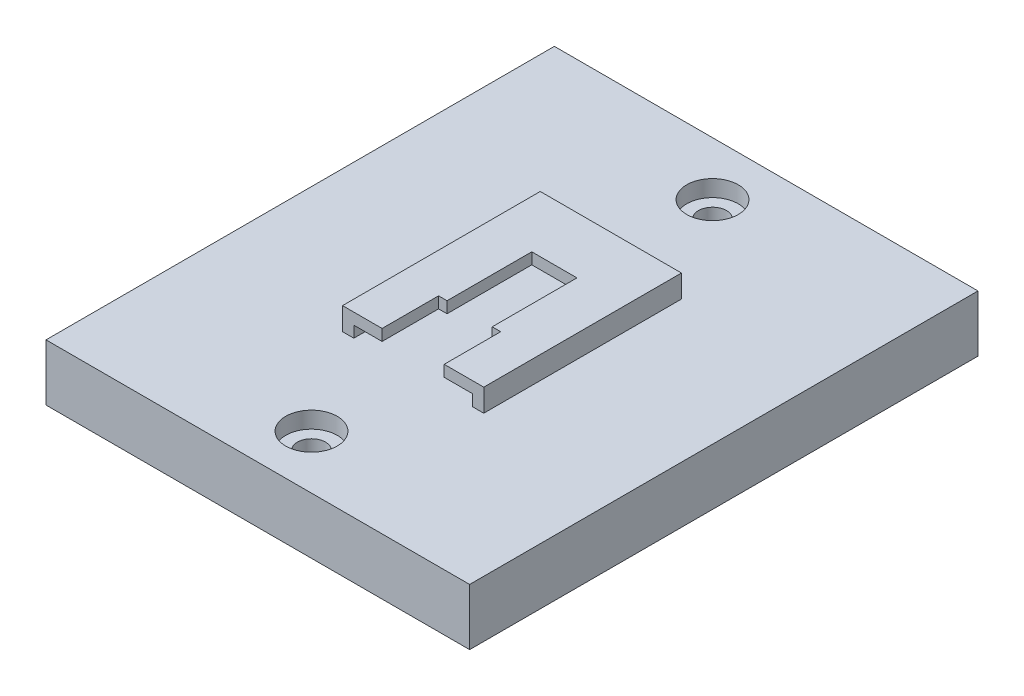
SolidWorks part; units mm, degrees
ref_plane "Front Plane" through (0, 0, 0) normal (0, 0, 1) x (1, 0, 0)
ref_plane "Top Plane" through (0, 0, 0) normal (0, 1, 0) x (1, 0, 0)
ref_plane "Right Plane" through (0, 0, 0) normal (1, 0, 0) x (0, 0, -1)
sketch "Sketch1" plane through (0, 0, 0) normal (0, 1, 0) x (1, 0, 0)
  line L0 (0, 23.0591) -> (0, -29.2863) construction
  line L1 (-12.5, 17.5) -> (12.5, 17.5)
  line L2 (-12.5, 17.5) -> (-12.5, -17.5)
  line L3 (-12.5, -17.5) -> (12.5, -17.5)
  line L4 (12.5, 17.5) -> (12.5, -17.5)
  line L5 (-12.5, 17.5) -> (12.5, -17.5) construction
  line L6 (-12.5, -17.5) -> (12.5, 17.5) construction
  line L7 (-5.5, -17.5) -> (5.5, -17.5)
  line L8 (-5.5, -17.5) -> (-5.5, -7.5)
  line L9 (-5.5, -7.5) -> (5.5, -7.5)
  line L10 (5.5, -17.5) -> (5.5, -7.5)
  line L11 (-4, -7.5) -> (4, -7.5)
  line L12 (-4, -7.5) -> (-4, 7.5)
  line L13 (-4, 7.5) -> (4, 7.5)
  line L14 (4, -7.5) -> (4, 7.5)
  point P0 (0, 0)
  point P16 (5.5, -20)
  dimension "D1" = 25
  dimension "D2" = 35
  dimension "D3" = 11
  dimension "D4" = 8
  dimension "D5" = 10
  dimension "D6" = 25
extrude "Boss-Extrude1" add sketch "Sketch1" along normal blind 2 contours L14 L9 L10 L3 L4 L1 L2 L8 L12 L13 region at (0, 0, -17.0699)
sketch "Sketch2" plane through (0, 0, 0) normal (0, -1, 0) x (1, 0, 0)
  line L0 (-12.5, 17.5) -> (-12.5, -17.5)
  line L1 (-12.5, -17.5) -> (12.5, -17.5)
  line L2 (12.5, -17.5) -> (12.5, 17.5)
  line L3 (12.5, 17.5) -> (10.5, 17.5)
  line L4 (5.5, 17.5) -> (12.5, 17.5) construction
  line L5 (10.5, 17.5) -> (10.5, -15.5)
  line L6 (10.5, -15.5) -> (-10.5, -15.5)
  line L7 (-10.5, -15.5) -> (-10.5, 17.5)
  line L8 (-12.5, 17.5) -> (-5.5, 17.5) construction
  line L9 (-10.5, 17.5) -> (-12.5, 17.5)
  point P4 (0, 0)
  dimension "D1" = 2
  dimension "D2" = 2
  dimension "D3" = 2
extrude "Boss-Extrude2" add sketch "Sketch2" along normal blind 2
sketch "Sketch3" plane through (0, -2, 0) normal (0, -1, 0) x (1, 0, 0)
  line L1 (-37.5, 45) -> (37.5, 45)
  line L2 (-37.5, 45) -> (-37.5, -45)
  line L3 (-37.5, -45) -> (37.5, -45)
  line L4 (37.5, 45) -> (37.5, -45)
  line L5 (-37.5, 45) -> (37.5, -45) construction
  line L6 (-37.5, -45) -> (37.5, 45) construction
  point P0 (0, 0)
  dimension "D1" = 75
  dimension "D2" = 90
extrude "Boss-Extrude3" add sketch "Sketch3" along normal blind 10
sketch "Sketch4" plane through (0, -2, 0) normal (0, 1, 0) x (1, 0, 0)
  line L0 (0, 52.8403) -> (0, -58.1898) construction
  line L1 (-26, 26) -> (26, 26) construction
  line L2 (-26, 26) -> (-26, -26) construction
  line L3 (-26, -26) -> (26, -26) construction
  line L4 (26, 26) -> (26, -26) construction
  line L5 (-26, 26) -> (26, -26) construction
  line L6 (-26, -26) -> (26, 26) construction
  line L7 (-11.2462, 35.5) -> (11.9137, 35.5) construction
  line L10 (-37.5, 45) -> (37.5, 45) construction
  line L11 (-7.7, 0) -> (7.7, 0) construction
  line L12 (-11.2462, -35.5) -> (11.9137, -35.5) construction
  point P0 (0, 0)
  point P10 (-11.2462, 35.3348)
  dimension "D1" = 52
  dimension "D2" = 52
  dimension "D3" = 9.5
hole_wizard "CBORE for #8 Pan Head Machine Screw1" positions "Sketch5" profile "Sketch6" counterbore size "#8" standard "ANSI Inch" end condition through all
sketch "Sketch5" plane through (0, -2, 0) normal (0, 1, 0) x (1, 0, 0)
  line L0 (0, 52.8403) -> (0, -58.1898) construction
  line L1 (-11.2462, 35.5) -> (11.9137, 35.5) construction
  line L2 (-11.2462, -35.5) -> (11.9137, -35.5) construction
  point P0 (0, 35.5)
  point P6 (0, -35.5)
sketch "Sketch6" plane through (0, -2, -35.5) normal (1, 0, 0) x (0, 0, 1)
  line L0 (0, 0) -> (0, 10)
  line L1 (0, 10) -> (2.4892, 10)
  line L3 (2.4892, 10) -> (2.4892, 2.921)
  line L4 (2.4892, 2.921) -> (4.5644, 2.921)
  line L5 (4.5644, 2.921) -> (4.5644, 0)
  line L7 (4.5644, 0) -> (0, 0)
  line L11 (0, -6.35) -> (0, 107.95) construction
  dimension "Thru Hole Dia." = 4.9784
  dimension "Thru Hole Depth" = 10
  dimension "C'Bore Dia." = 9.1288
  dimension "C'Bore Depth" = 2.921
